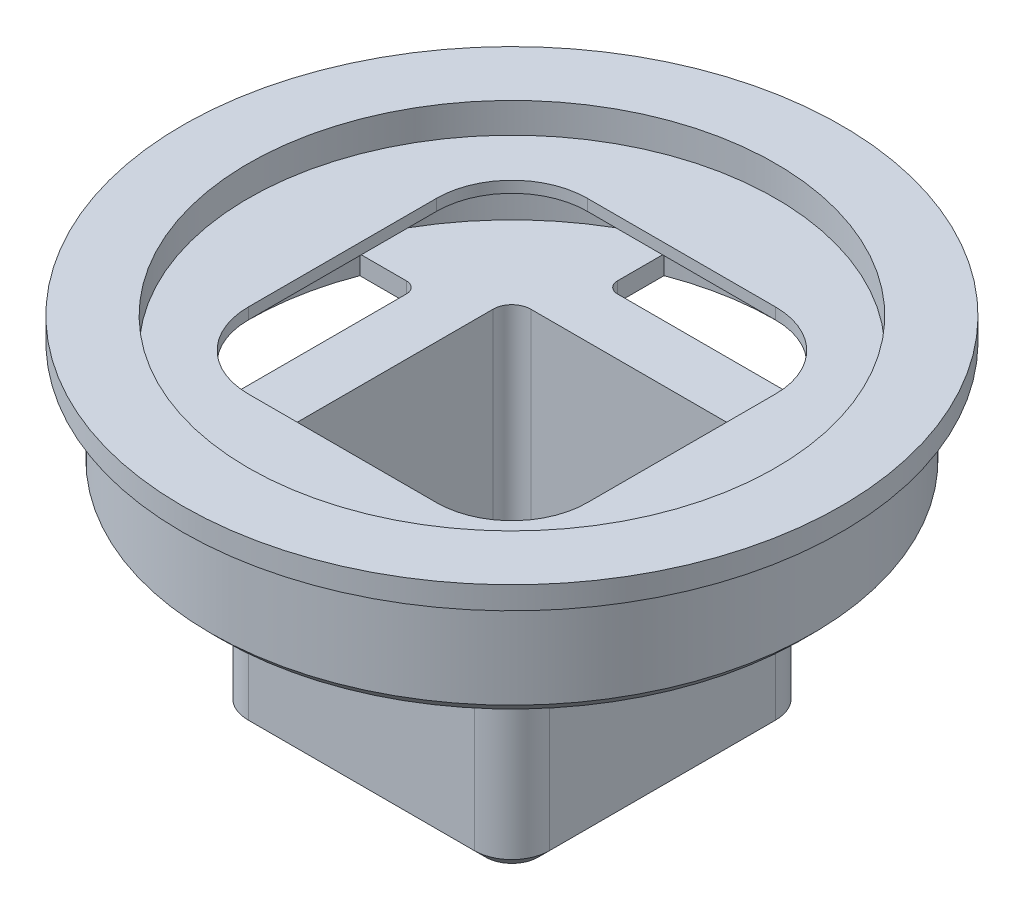
SolidWorks part; units mm, degrees
material "PBT General Purpose"
ref_plane "Front Plane" through (0, 0, 0) normal (0, 0, 1) x (1, 0, 0)
ref_plane "Top Plane" through (0, 0, 0) normal (0, 1, 0) x (1, 0, 0)
ref_plane "Right Plane" through (0, 0, 0) normal (1, 0, 0) x (0, 0, -1)
sketch "Sketch1" plane through (0, 0, 0) normal (0, 1, 0) x (1, 0, 0)
  circle A0 centre (0, 0) radius 80
  dimension "D1" = 160
extrude "Boss-Extrude1" add sketch "Sketch1" along normal blind 25
sketch "Sketch2" plane through (0, 25, 0) normal (0, 1, 0) x (1, 0, 0)
  circle A0 centre (0, 0) radius 70
  circle A2 centre (0, 0) radius 80
  circle A3 centre (0, 0) radius 80
  dimension "D2" = 140
  dimension "D1" = 0
extrude "Boss-Extrude2" add sketch "Sketch2" along normal blind 5
sketch "Sketch3" plane through (0, 30, 0) normal (0, 1, 0) x (1, 0, 0)
  circle A0 centre (0, 0) radius 87.5
  circle A1 centre (0, 0) radius 70
  dimension "D1" = 175
extrude "Boss-Extrude3" add sketch "Sketch3" along normal blind 6 contours A0 | A1
sketch "Sketch5" plane through (0, 0, 0) normal (0, -1, 0) x (1, 0, 0)
  line L1 (-40, 40) -> (40, 40)
  line L2 (-40, 40) -> (-40, -40)
  line L3 (-40, -40) -> (40, -40)
  line L4 (40, 40) -> (40, -40)
  line L5 (-40, 40) -> (40, -40) construction
  line L6 (-40, -40) -> (40, 40) construction
  point P0 (0, 0)
  dimension "D1" = 80
extrude "Boss-Extrude4" add sketch "Sketch5" along normal blind 55
shell "Shell1" thickness 5 removed face at (0, 25, 70)
hole_wizard "Ø6.3 (6.3) Diameter Hole1" positions "Sketch8" profile "Sketch7" hole size "Ø6.3" standard "ISO"
sketch "Sketch8" plane through (0, -50, 0) normal (0, 1, 0) x (1, 0, 0)
  line L1 (-24, 24) -> (24, 24)
  line L2 (-24, 24) -> (-24, -24)
  line L3 (-24, -24) -> (24, -24)
  line L4 (24, 24) -> (24, -24)
  line L5 (-24, 24) -> (24, -24) construction
  line L6 (-24, -24) -> (24, 24) construction
  line L8 (-8, 8) -> (8, 8)
  line L9 (-8, 8) -> (-8, -8)
  line L10 (-8, -8) -> (8, -8)
  line L11 (8, 8) -> (8, -8)
  line L12 (-8, 8) -> (8, -8) construction
  line L13 (-8, -8) -> (8, 8) construction
  line L14 (8, 24) -> (8, 8) construction
  line L17 (24, 8) -> (8, 8) construction
  line L19 (-8, 24) -> (-8, 8) construction
  line L22 (-8, 8) -> (-24, 8) construction
  line L24 (-24, -8) -> (-8, -8) construction
  line L28 (-8, -8) -> (-8, -24) construction
  line L30 (8, -8) -> (8, -24) construction
  line L32 (8, -8) -> (24, -8) construction
  point P1 (0, 0)
  point P2 (24, -24)
  point P73 (-24, 24)
  point P74 (-24, -24)
  point P75 (24, 24)
  point P77 (0, 0)
  point P78 (8, -8)
  point P161 (-8, 8)
  point P162 (-8, -8)
  point P163 (8, 8)
  point P166 (8, 24)
  point P171 (24, 8)
  point P174 (-8, 24)
  point P181 (-24, 8)
  point P183 (-24, -8)
  point P193 (-8, -24)
  point P198 (8, -24)
  point P202 (24, -8)
  dimension "D1" = 48
  dimension "D2" = 16
sketch "Sketch7" plane through (0, -50, 0) normal (1, 0, 0) x (0, 0, 1)
  line L0 (0, 0) -> (0, 11.8927)
  line L1 (0, 11.8927) -> (3.15, 10)
  line L2 (3.15, 10) -> (3.15, 0)
  line L5 (3.15, 0) -> (0, 0)
  line L10 (0, 11.8927) -> (-3.15, 10) construction
  line L11 (0, -6.35) -> (0, 107.95) construction
  dimension "Hole Dia." = 6.3
  dimension "Hole Depth" = 10
  dimension "Drill Angle" = 118
sketch "Sketch9" plane through (0, -50, 0) normal (0, 1, 0) x (1, 0, 0)
  circle A0 centre (0, 0) radius 5.6238
extrude "Boss-Extrude5" add sketch "Sketch9" against normal blind 5
sketch "Sketch10" plane through (0, 5, 0) normal (0, 1, 0) x (1, 0, 0)
  line L0 (0, 75) -> (0, 35) construction
  line L1 (-35, 35) -> (35, 35) construction
  line L2 (-35, 35) -> (35, 35) construction
  line L3 (-2, 46.5) -> (-29.5, 46.5)
  line L4 (-2, 46.5) -> (-2, 42.5)
  line L5 (-2, 42.5) -> (-29.5, 42.5)
  line L6 (-29.5, 46.5) -> (-29.5, 42.5)
  line L7 (2, 46.5) -> (29.5, 46.5)
  line L8 (2, 46.5) -> (2, 42.5)
  line L9 (2, 42.5) -> (29.5, 42.5)
  line L10 (29.5, 46.5) -> (29.5, 42.5)
  line L11 (-22, 54.5) -> (-2, 54.5)
  line L12 (-22, 54.5) -> (-22, 50.5)
  line L13 (-22, 50.5) -> (-2, 50.5)
  line L14 (-2, 54.5) -> (-2, 50.5)
  line L15 (2, 54.5) -> (22, 54.5)
  line L16 (2, 54.5) -> (2, 50.5)
  line L17 (2, 50.5) -> (22, 50.5)
  line L18 (22, 54.5) -> (22, 50.5)
  line L19 (-16, 62.5) -> (-2, 62.5)
  line L20 (-16, 62.5) -> (-16, 58.5)
  line L21 (-16, 58.5) -> (-2, 58.5)
  line L22 (-2, 62.5) -> (-2, 58.5)
  line L23 (2, 62.5) -> (16, 62.5)
  line L24 (2, 62.5) -> (2, 58.5)
  line L25 (2, 58.5) -> (16, 58.5)
  line L26 (16, 62.5) -> (16, 58.5)
  circle A0 centre (0, 0) radius 75 construction
  circle A1 centre (0, 0) radius 75 construction
  dimension "D1" = 4
  dimension "D2" = 4
  dimension "D3" = 4
  dimension "D4" = 7.5
  dimension "D5" = 27.5
  dimension "D6" = 20
  dimension "D7" = 14
  dimension "D8" = 4
ref_plane "Plane1" through (0, 25, 0) normal (0, 1, 0) x (1, 0, 0)
sketch "Sketch11" plane through (0, 25, 0) normal (0, 1, 0) x (1, 0, 0)
  line L12 (-45, 25) -> (-45, -25)
  line L13 (-25, -45) -> (25, -45)
  line L14 (45, -25) -> (45, 25)
  line L15 (25, 45) -> (-25, 45)
  circle A0 centre (0, 0) radius 70
  arc A13 (-45, -25) -> (-25, -45) centre (-25, -25) ccw
  arc A14 (25, -45) -> (45, -25) centre (25, -25) ccw
  arc A15 (45, 25) -> (25, 45) centre (25, 25) ccw
  arc A16 (-25, 45) -> (-45, 25) centre (-25, 25) ccw
extrude "Boss-Extrude6" add sketch "Sketch11" along normal blind 3
sketch "Sketch12" plane through (0, 0, 0) normal (0, -1, 0) x (1, 0, 0)
  line L4 (-50, 25) -> (-65.3835, 25)
  line L5 (-25, 50) -> (-25, 65.3835)
  line L6 (25, 50) -> (25, 65.3835)
  line L7 (50, 25) -> (65.3835, 25)
  line L8 (-50, -25) -> (-50, 25)
  line L9 (-25, 50) -> (25, 50)
  line L10 (50, 25) -> (50, -25)
  line L11 (25, -50) -> (-25, -50)
  line L12 (50, -25) -> (65.3835, -25)
  line L13 (25, -50) -> (25, -65.3835)
  line L14 (-25, -50) -> (-25, -65.3835)
  line L15 (-50, -25) -> (-65.3835, -25)
  arc A0 (-65.3835, 25) -> (-65.3835, -25) centre (0, 0) ccw
  arc A1 (25, 65.3835) -> (-25, 65.3835) centre (0, 0) ccw
  arc A2 (65.3835, -25) -> (65.3835, 25) centre (0, 0) ccw
  arc A3 (-25, -65.3835) -> (25, -65.3835) centre (0, 0) ccw
extrude "Cut-Extrude2" cut sketch "Sketch12" against normal blind 6
fillet "Fillet2" radius 3 8 edges at (50, 2.5, -25) (50, 2.5, 25) (25, 2.5, -50) (-25, 2.5, -50) (-50, 2.5, -25) (-50, 2.5, 25) (25, 2.5, 50) (-25, 2.5, 50)
sketch "Sketch18" plane through (0, -55, 0) normal (0, -1, 0) x (1, 0, 0)
  circle A0 centre (0, 0) radius 15.8801
extrude "Boss-Extrude9" add sketch "Sketch18" against normal blind 5
sketch "Sketch19" plane through (0, -55, 0) normal (0, -1, 0) x (1, 0, 0)
  circle A0 centre (0, 0) radius 10
  dimension "D1" = 20
extrude "Boss-Extrude10" add sketch "Sketch19" against normal blind 10
hole_wizard "CBORE for M6 Hex Socket Head Cap Screw1" positions "Sketch21" profile "Sketch20" counterbore size "M6" standard "ISO" end condition through all
sketch "Sketch21" plane through (0, -55, 0) normal (0, -1, 0) x (-1, 0, 0)
  point P0 (0, 0)
sketch "Sketch20" plane through (0, -55, 0) normal (1, 0, 0) x (0, 0, -1)
  line L0 (0, 0) -> (0, 91)
  line L1 (0, 91) -> (3.3, 91)
  line L3 (3.3, 91) -> (3.3, 6.4)
  line L4 (3.3, 6.4) -> (5.5, 6.4)
  line L5 (5.5, 6.4) -> (5.5, 0)
  line L7 (5.5, 0) -> (0, 0)
  line L11 (0, -6.35) -> (0, 107.95) construction
  dimension "Thru Hole Dia." = 6.6
  dimension "Thru Hole Depth" = 91
  dimension "C'Bore Dia." = 11
  dimension "C'Bore Depth" = 6.4
fillet "Fillet7" radius 10 4 edges at (-40, -27.5, -40) (40, -27.5, -40) (40, -27.5, 40) (-40, -27.5, 40)
fillet "Fillet8" radius 5 4 edges at (35, -22.5, 35) (35, -22.5, -35) (-35, -22.5, -35) (-35, -22.5, 35)
chamfer "Chamfer1" distance 3 angle 45 9 edges at (0, 0, 80) (0, -55, -40) (-40, -55, 0) (0, -55, 40) (40, -55, 0) (-37.0711, -55, -37.0711) (-37.0711, -55, 37.0711) (37.0711, -55, -37.0711) (37.0711, -55, 37.0711)
